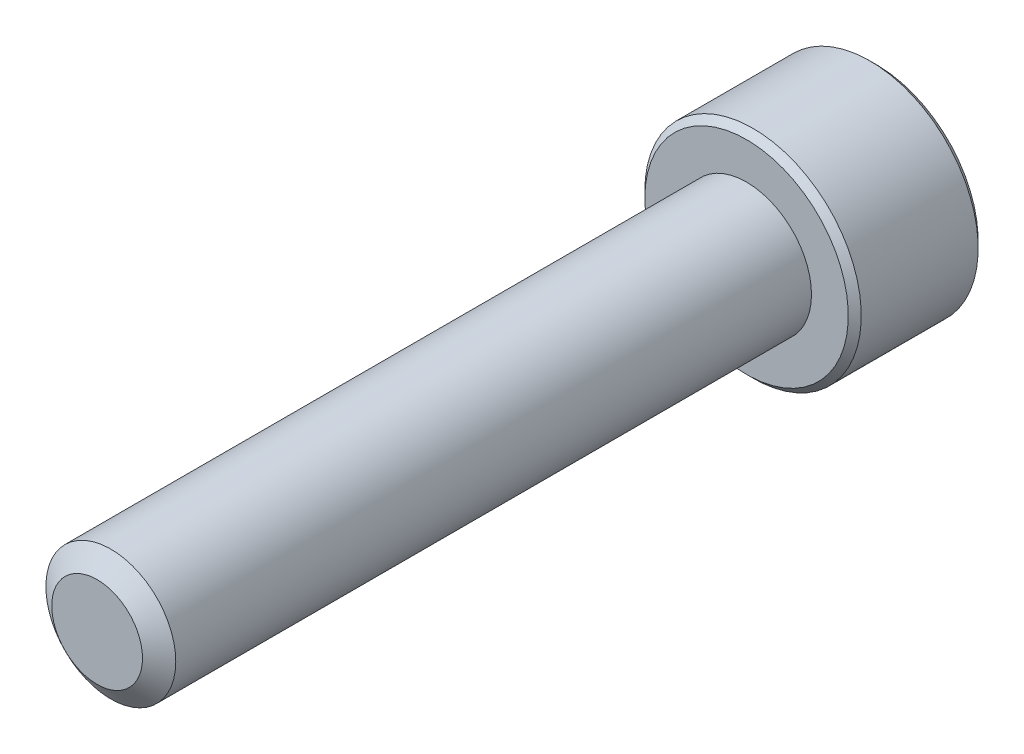
SolidWorks part; units mm, degrees
material "Alloy Steel"
ref_plane "Front Plane" through (0, 0, 0) normal (0, 0, 1) x (1, 0, 0)
ref_plane "Top Plane" through (0, 0, 0) normal (0, 1, 0) x (1, 0, 0)
ref_plane "Right Plane" through (0, 0, 0) normal (1, 0, 0) x (0, 0, -1)
sketch "Sketch1" plane through (0, 0, 0) normal (0, 0, 1) x (1, 0, 0)
  circle A0 centre (0, 0) radius 3
  dimension "OD" = 6
extrude "Extrude1" add sketch "Sketch1" against normal blind 30
sketch "Sketch2" plane through (0, 0, 0) normal (0, 0, 1) x (1, 0, 0)
  circle A0 centre (0, 0) radius 3 construction
  circle A1 centre (0, 0) radius 3
curve "Helix/Spiral1" pitch 1 height 31 turns 31 parameters "pitch"=1
sketch "Sketch3" plane through (0, 0, 0) normal (1, 0, 0) x (0, 0, -1)
  line L0 (-0.875, 3) -> (-0.5, 2.3505)
  line L1 (-0.5, 2.3505) -> (-0.375, 2.3505)
  line L2 (-0.375, 2.3505) -> (0, 3)
  line L3 (-0.875, 3) -> (0, 3)
  line L4 (-0.4375, 3) -> (-0.4375, 2.3505) construction
  line L5 (-0.6875, 2.6752) -> (-0.1875, 2.6752) construction
  line L6 (0, 3) -> (0, -3) construction
  line L7 (0, -3) -> (30, -3) construction
  point P11 (4.5, -3)
  dimension "D1" = 0.125
  dimension "D2" = 0.5
  dimension "D3" = 60
  dimension "D4" = 4.5
sweep "Cut-Sweep1" [suppressed] cut profiles "Sketch3" path "Helix/Spiral1"
sketch "Sketch4" plane through (0, 0, 0) normal (1, 0, 0) x (0, 0, -1)
  line L0 (0.6327, 3) -> (0, 2.0965)
  line L1 (0, 2.0965) -> (0, 3)
  line L2 (0.6327, 3) -> (0, 3)
  line L3 (-0.875, 3) -> (0, 3) construction
  line L4 (0, 0) -> (7.0209, 0) construction
  dimension "D1" = 55
  dimension "D2" = 0.254
revolve "Cut-Revolve1" cut sketch "Sketch4" angle 360 about L4
sketch "Sketch5" [suppressed] plane through (0, 0, 0) normal (1, 0, 0) x (0, 0, -1)
  line L0 (30, -2.3644) -> (30, 2.1406) construction
  line L1 (30, 3) -> (0.1203, 3)
  line L2 (30, 3) -> (30, 0)
  line L3 (30, 0) -> (0.0001, 0)
  line L4 (0.0001, 2.6698) -> (0.0001, 0)
  line L5 (0.1203, 3) -> (0.0001, 2.6698)
  line L6 (0, 0) -> (9.9695, 0) construction
  point P3 (0.0001, 3)
  point P10 (0.0001, 3)
  dimension "D1" = 0.3302
  dimension "Thread min" = 0.0001
  dimension "D3" = 20
revolve "partially thread" [suppressed] add sketch "Sketch5" angle 360 about L6
sketch "Sketch6" plane through (0, 0, -30) normal (0, 0, -1) x (-1, 0, 0)
  circle A0 centre (0, 0) radius 5
  dimension "head dia" = 10
extrude "Extrude2" add sketch "Sketch6" along normal blind 6
sketch "Sketch7" plane through (0, 0, -36) normal (0, 0, -1) x (-1, 0, 0)
  line L1 (0, 2.8868) -> (-2.5, 1.4434)
  line L2 (-2.5, 1.4434) -> (-2.5, -1.4434)
  line L3 (-2.5, -1.4434) -> (0, -2.8868)
  line L4 (0, -2.8868) -> (2.5, -1.4434)
  line L5 (2.5, -1.4434) -> (2.5, 1.4434)
  line L6 (2.5, 1.4434) -> (0, 2.8868)
  circle A0 centre (0, 0) radius 2.5 construction
  dimension "hex dia" = 5
extrude "Cut-Extrude1" cut sketch "Sketch7" against normal blind 3.75
sketch "Sketch8" plane through (0, 0, -36) normal (0, 0, -1) x (-1, 0, 0)
  circle A0 centre (0, 0) radius 2.8868
extrude "Cut-Extrude2" cut sketch "Sketch8" against normal through all draft 45
chamfer "Chamfer1" distance 0.3 angle 45 2 edges at (-5, 0, -36) (-5, 0, -30)
sketch "Sketch9" plane through (0, 0, 0) normal (1, 0, 0) x (0, 0, -1)
  line L0 (0, 3) -> (0, -3) construction
  line L1 (5.5, 3) -> (5.5, -3) construction
  dimension "D1" = 5.5
sketch "Sketch10" plane through (0, 0, 0) normal (1, 0, 0) x (0, 0, -1)
  line L0 (30, 3) -> (30, 0)
  line L1 (30, 3) -> (29.75, 3)
  line L2 (29.75, 3) -> (28.5074, 0)
  line L3 (30, 0) -> (28.5074, 0)
  line L4 (30, 4.7) -> (30, -4.7) construction
  dimension "D1" = 22.5
  dimension "D2" = 0.25
revolve "Revolve1" add sketch "Sketch10" angle 360 about L3
equation "\"D3@Helix/Spiral1\" = \"screw length@Extrude1\"+\"pitch@Helix/Spiral1\""
equation "\"D1@Sketch3\" = \"pitch@Helix/Spiral1\"*.125"
equation "\"D2@Sketch3\" = \"pitch@Helix/Spiral1\"*.5"
equation "\"D1@Cut-Extrude1\" = \"hex dia@Sketch7\"*.75"
equation "\"D1@Chamfer1\" = \"head dia@Sketch6\"*.03"
equation "\"D1@Sketch9\" = \"pitch@Helix/Spiral1\"*5.5"
equation "\"D2@Sketch10\" = \"pitch@Helix/Spiral1\"*.25"
equation "\"D4@Sketch3\" = \"pitch@Helix/Spiral1\"*4.50"
